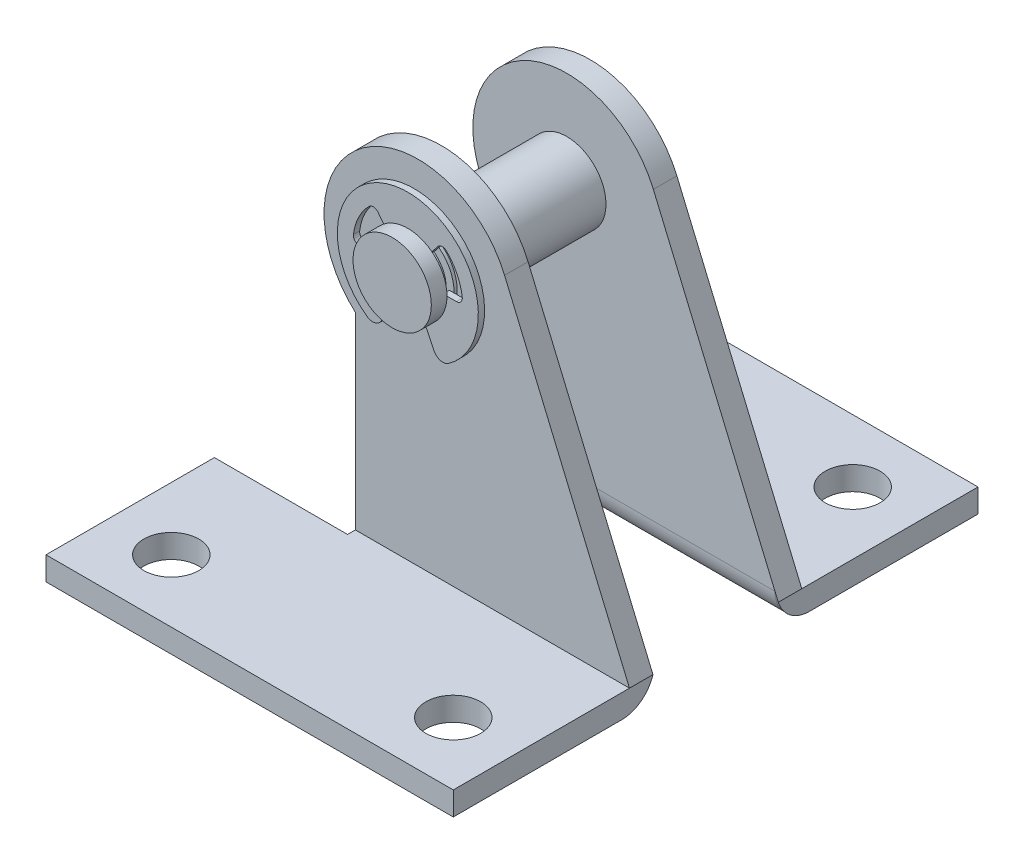
SolidWorks part; units mm, degrees
ref_plane "前视基准面" through (0, 0, 0) normal (0, 0, 1) x (1, 0, 0)
ref_plane "上视基准面" through (0, 0, 0) normal (0, 1, 0) x (1, 0, 0)
ref_plane "右视基准面" through (0, 0, 0) normal (1, 0, 0) x (0, 0, -1)
sketch "草图1" plane through (0, 0, 0) normal (1, 0, 0) x (0, 0, -1)
  line L0 (-14.3, 0) -> (-14.3, 5)
  line L1 (-14.3, 5) -> (-12.3, 5)
  line L2 (-12.3, 5) -> (-12.3, 4)
  line L3 (-12.3, 4) -> (-11.4, 4)
  line L4 (-11.4, 4) -> (-11.4, 5)
  line L5 (-11.4, 5) -> (11.4, 5)
  line L6 (11.4, 5) -> (11.4, 4)
  line L7 (11.4, 4) -> (12.3, 4)
  line L8 (12.3, 4) -> (12.3, 5)
  line L9 (12.3, 5) -> (14.3, 5)
  line L10 (14.3, 5) -> (14.3, 0)
  line L11 (14.3, 0) -> (-14.3, 0)
  line L12 (14.3, 0) -> (-14.3, 0) construction
revolve "旋转1" add sketch "草图1" angle 360 about L12 reverse direction yes
sketch "草图2" plane through (0, 0, 0) normal (0, 0, 1) x (1, 0, 0)
  line L0 (-8, -8.9443) -> (-8, -36)
  line L1 (-8, -36) -> (27, -36)
  line L2 (27, -36) -> (27, -33)
  line L3 (27, -33) -> (11.0507, 4.6778)
  arc A0 (11.0507, 4.6778) -> (-8, -8.9443) centre (0, 0) ccw
extrude "凸台-拉伸1" add sketch "草图2" against normal blind 11 and the other way blind 11
sketch "草图3" plane through (0, 0, 0) normal (1, 0, 0) x (0, 0, -1)
  line L0 (-8, 61) -> (-8, 5)
  line L1 (-8, 5) -> (8, 5)
  line L2 (8, 5) -> (8, 61)
  line L3 (8, 61) -> (-8, 61)
  line L4 (10, 0) -> (-10, 0) construction
revolve "切除-旋转1" cut sketch "草图3" angle 360 about L4 reverse direction yes
ref_plane "基准面4" through (0, -36, 0) normal (0, 1, 0) x (1, 0, 0)
sketch "草图4" plane through (0, -36, 0) normal (0, 1, 0) x (1, 0, 0)
  line L0 (-25, 33.5) -> (-25, -33.5)
  line L1 (-25, -33.5) -> (27, -33.5)
  line L2 (27, -33.5) -> (27, -8)
  line L3 (27, -8) -> (-8, -8)
  line L4 (-8, -8) -> (-8, 8)
  line L5 (-8, 8) -> (27, 8)
  line L6 (27, 8) -> (27, 33.5)
  line L7 (27, 33.5) -> (-25, 33.5)
  circle A0 centre (19, 25.5) radius 3.5
  circle A1 centre (19, -25.5) radius 3.5
  circle A2 centre (-17, 25.5) radius 3.5
  circle A3 centre (-17, -25.5) radius 3.5
extrude "凸台-拉伸2" add sketch "草图4" along normal blind 3
ref_plane "基准面5" through (-8, 0, 0) normal (1, 0, 0) x (0, 0, -1)
sketch "草图5" plane through (-8, 0, 0) normal (1, 0, 0) x (0, 0, -1)
  line L0 (-12, -33) -> (-12, -36)
  line L1 (-12, -36) -> (12, -36)
  line L2 (12, -36) -> (12, -33)
  line L3 (12, -33) -> (-12, -33)
extrude "切除-拉伸1" cut sketch "草图5" against normal blind 18
ref_plane "基准面6" through (0, 0, 12.3) normal (0, 0, 1) x (1, 0, 0)
sketch "草图6" plane through (0, 0, 12.3) normal (0, 0, 1) x (1, 0, 0)
  line L0 (-3.3529, -6.8745) -> (-1.9727, -4.0446)
  line L1 (-4.5, 0) -> (-6.2048, 0)
  line L2 (-3.8201, 4.8895) -> (-2.7705, 3.546)
  line L3 (2.7705, 3.546) -> (3.8201, 4.8895)
  line L4 (6.2048, 0) -> (4.5, 0)
  line L5 (1.9727, -4.0446) -> (3.3529, -6.8745)
  arc A0 (5.1984, -7.3469) -> (-5.1984, -7.3469) centre (0, 0) ccw
  arc A1 (-5.1984, -7.3469) -> (-3.3529, -6.8745) centre (-4.4764, -6.3265) ccw
  arc A2 (-1.9727, -4.0446) -> (-4.5, 0) centre (0, 0) cw
  arc A3 (-6.2048, 0) -> (-6.9494, 0.84) centre (-6.2048, 0.75) cw
  arc A4 (-6.9494, 0.84) -> (-4.9404, 4.9591) centre (0, 0) cw
  arc A5 (-4.9404, 4.9591) -> (-3.8201, 4.8895) centre (-4.4111, 4.4277) cw
  arc A6 (-2.7705, 3.546) -> (2.7705, 3.546) centre (0, 0) cw
  arc A7 (3.8201, 4.8895) -> (4.9404, 4.9591) centre (4.4111, 4.4277) cw
  arc A8 (4.9404, 4.9591) -> (6.9494, 0.84) centre (0, 0) cw
  arc A9 (6.9494, 0.84) -> (6.2048, 0) centre (6.2048, 0.75) cw
  arc A10 (4.5, 0) -> (1.9727, -4.0446) centre (0, 0) cw
  arc A11 (3.3529, -6.8745) -> (5.1984, -7.3469) centre (4.4764, -6.3265) ccw
extrude "凸台-拉伸3" add sketch "草图6" against normal blind 0.8
ref_plane "基准面7" through (0, 0, -12.3) normal (0, 0, 1) x (1, 0, 0)
sketch "草图7" plane through (0, 0, -12.3) normal (0, 0, 1) x (1, 0, 0)
  line L0 (-3.3529, -6.8745) -> (-1.9727, -4.0446)
  line L1 (-4.5, 0) -> (-6.2048, 0)
  line L2 (-3.8201, 4.8895) -> (-2.7705, 3.546)
  line L3 (2.7705, 3.546) -> (3.8201, 4.8895)
  line L4 (6.2048, 0) -> (4.5, 0)
  line L5 (1.9727, -4.0446) -> (3.3529, -6.8745)
  arc A0 (5.1984, -7.3469) -> (-5.1984, -7.3469) centre (0, 0) ccw
  arc A1 (-5.1984, -7.3469) -> (-3.3529, -6.8745) centre (-4.4764, -6.3265) ccw
  arc A2 (-1.9727, -4.0446) -> (-4.5, 0) centre (0, 0) cw
  arc A3 (-6.2048, 0) -> (-6.9494, 0.84) centre (-6.2048, 0.75) cw
  arc A4 (-6.9494, 0.84) -> (-4.9404, 4.9591) centre (0, 0) cw
  arc A5 (-4.9404, 4.9591) -> (-3.8201, 4.8895) centre (-4.4111, 4.4277) cw
  arc A6 (-2.7705, 3.546) -> (2.7705, 3.546) centre (0, 0) cw
  arc A7 (3.8201, 4.8895) -> (4.9404, 4.9591) centre (4.4111, 4.4277) cw
  arc A8 (4.9404, 4.9591) -> (6.9494, 0.84) centre (0, 0) cw
  arc A9 (6.9494, 0.84) -> (6.2048, 0) centre (6.2048, 0.75) cw
  arc A10 (4.5, 0) -> (1.9727, -4.0446) centre (0, 0) cw
  arc A11 (3.3529, -6.8745) -> (5.1984, -7.3469) centre (4.4764, -6.3265) ccw
extrude "凸台-拉伸4" add sketch "草图7" along normal blind 0.8
fillet "圆角1" radius 4 2 edges at (9.5, -36, 8) (9.5, -36, -8)
ref_plane "sdb XY" through (0, 0, 0) normal (0, 0, 1) x (1, 0, 0)
ref_plane "sdb XZ" through (0, 0, 0) normal (0, -1, 0) x (-1, 0, 0)
ref_plane "sdb YZ" through (0, 0, 0) normal (1, 0, 0) x (0, 0, -1)
ref_axis "sdb X" through (-80.9, 0, 0) along (1, 0, 0)
ref_axis "sdb Y" through (0, -50, 0) along (0, 1, 0)
ref_axis "sdb Z" through (0, 0, 80.9) along (0, 0, -1)
sketch3d "sdb"
  point P0 (0, 0, 0)
